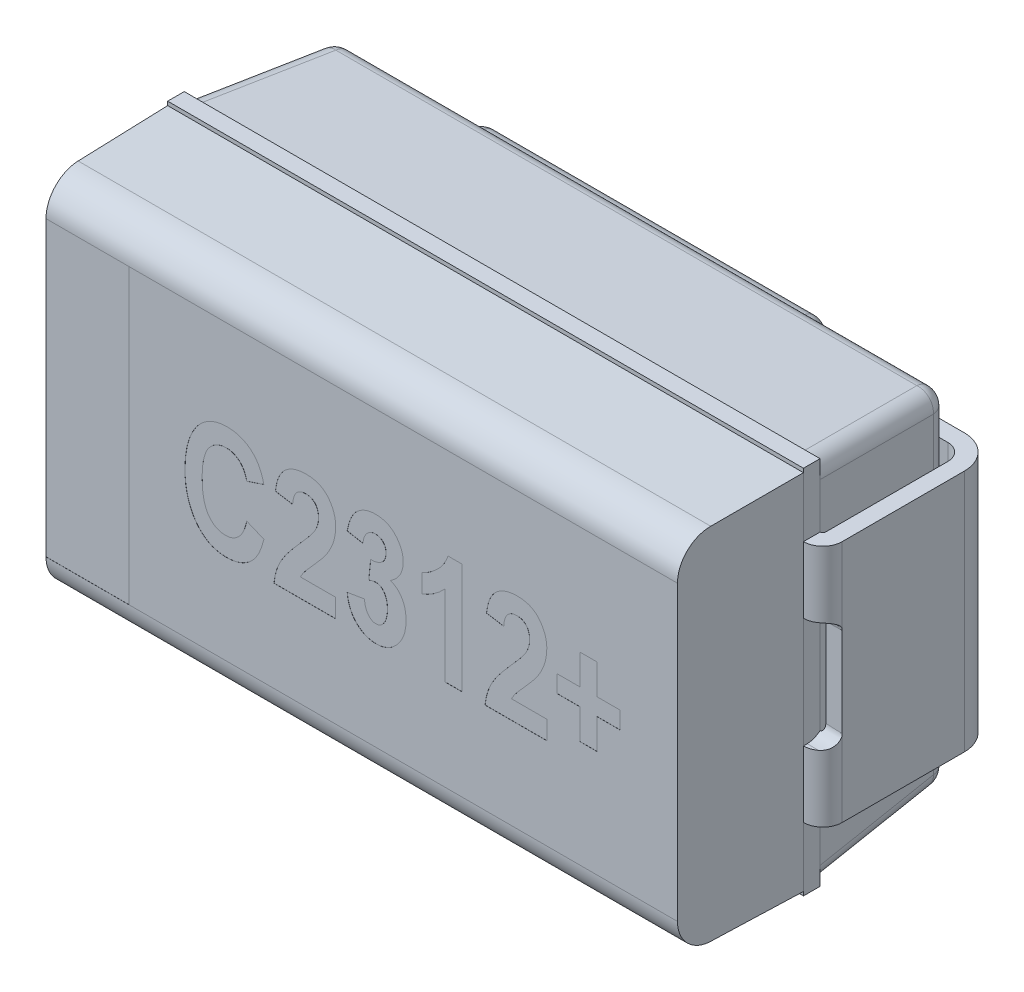
SolidWorks part; units mm, degrees
ref_plane "Front Plane" through (0, 0, 0) normal (0, 0, 1) x (1, 0, 0)
ref_plane "Top Plane" through (0, 0, 0) normal (0, 1, 0) x (1, 0, 0)
ref_plane "Right Plane" through (0, 0, 0) normal (1, 0, 0) x (0, 0, -1)
sketch "Sketch1" plane through (0, 0, 0) normal (0, 0, 1) x (1, 0, 0)
  line L1 (-2.875, 1.66) -> (2.875, 1.66)
  line L2 (-2.875, 1.66) -> (-2.875, -1.66)
  line L3 (-2.875, -1.66) -> (2.875, -1.66)
  line L4 (2.875, 1.66) -> (2.875, -1.66)
  line L5 (-2.875, 1.66) -> (2.875, -1.66) construction
  line L6 (-2.875, -1.66) -> (2.875, 1.66) construction
  point P0 (0, 0)
  dimension "D1" = 3.32
  dimension "D2" = 5.75
extrude "Boss-Extrude1" add sketch "Sketch1" against normal blind 1.26 draft 5 from offset 1.43 contours L2 L3 L4 L1
fillet "Fillet2" radius 0.15 8 edges at (-2.7648, 0, 0.17) (0, -1.5498, 0.17) (2.7648, 0, 0.17) (0, 1.5498, 0.17) (2.8199, 1.6049, 0.8) (-2.8199, 1.6049, 0.8) (2.8199, -1.6049, 0.8) (-2.8199, -1.6049, 0.8)
sketch "Sketch3" plane through (0, 0, 1.43) normal (0, 0, 1) x (1, 0, 0)
  line L0 (2.875, 1.5106) -> (2.875, -1.5106) construction
  line L1 (-2.875, 1.675) -> (2.875, 1.675)
  line L2 (-2.875, 1.675) -> (-2.875, -1.675)
  line L3 (-2.875, -1.675) -> (2.875, -1.675)
  line L4 (2.875, 1.675) -> (2.875, -1.675)
  line L5 (-2.875, 1.675) -> (2.875, -1.675) construction
  line L6 (-2.875, -1.675) -> (2.875, 1.675) construction
  point P0 (0, 0)
  dimension "D1" = 3.35
extrude "Boss-Extrude2" add sketch "Sketch3" along normal blind 0.15
sketch "Sketch4" plane through (0, 0, 1.58) normal (0, 0, 1) x (1, 0, 0)
  line L0 (2.875, -1.675) -> (2.875, 1.675) construction
  line L1 (-2.875, 1.64) -> (2.875, 1.64)
  line L2 (-2.875, 1.64) -> (-2.875, -1.64)
  line L3 (-2.875, -1.64) -> (2.875, -1.64)
  line L4 (2.875, 1.64) -> (2.875, -1.64)
  line L5 (-2.875, 1.64) -> (2.875, -1.64) construction
  line L6 (-2.875, -1.64) -> (2.875, 1.64) construction
  point P0 (0, 0)
  dimension "D1" = 3.28
extrude "Boss-Extrude4" add sketch "Sketch4" along normal blind 1.12 draft 1
fillet "Fillet4" radius 0.3012 2 edges at (0, -1.6205, 2.7) (0, 1.6205, 2.7)
sketch "Sketch5" plane through (0, 0, 0.17) normal (0, 0, -1) x (-1, 0, 0)
  line L1 (-1.6, 1.45) -> (1.6, 1.45)
  line L2 (-1.6, 1.45) -> (-1.6, -1.45)
  line L3 (-1.6, -1.45) -> (1.6, -1.45)
  line L4 (1.6, 1.45) -> (1.6, -1.45)
  line L5 (-1.6, 1.45) -> (1.6, -1.45) construction
  line L6 (-1.6, -1.45) -> (1.6, 1.45) construction
  point P0 (0, 0)
  dimension "D1" = 3.2
  dimension "D2" = 2.9
extrude "Boss-Extrude5" add sketch "Sketch5" along normal blind 0.16 from offset 0.01 offset against normal yes
fillet "Fillet5" radius 0.15 8 edges at (0, -1.45, 0.02) (1.6, 0, 0.02) (0, 1.45, 0.02) (-1.6, 0, 0.02) (-1.6, 1.45, 0.0974) (-1.6, -1.45, 0.0974) (1.6, 1.45, 0.0974) (1.6, -1.45, 0.0974)
sketch "Sketch7" plane through (0, 0, 0) normal (0, 1, 0) x (1, 0, 0)
  line L0 (2.875, -1.58) -> (2.875, -1.43)
  line L1 (2.9, -1.405) -> (2.9, -0.3)
  line L2 (2.75, -0.15) -> (1.779, -0.15)
  line L3 (1.779, -0.15) -> (1.779, 0)
  line L4 (1.779, 0) -> (2.75, 0)
  line L5 (3.05, -0.3) -> (3.05, -1.405)
  line L7 (2.6273, -0.17) -> (1.5494, -0.17) construction
  line L8 (0, 0) -> (0, -2.7) construction
  line L9 (-2.8555, -2.7) -> (2.8555, -2.7) construction
  line L10 (-3.05, -0.3) -> (-3.05, -1.405)
  line L11 (-1.779, 0) -> (-2.75, 0)
  line L12 (-1.779, -0.15) -> (-1.779, 0)
  line L13 (-2.75, -0.15) -> (-1.779, -0.15)
  line L14 (-2.9, -1.405) -> (-2.9, -0.3)
  line L15 (-2.875, -1.58) -> (-2.875, -1.43)
  arc A0 (2.875, -1.43) -> (2.9, -1.405) centre (2.875, -1.405) ccw
  arc A1 (2.9, -0.3) -> (2.75, -0.15) centre (2.75, -0.3) ccw
  arc A2 (2.75, 0) -> (3.05, -0.3) centre (2.75, -0.3) cw
  arc A3 (3.05, -1.405) -> (2.875, -1.58) centre (2.875, -1.405) cw
  arc A4 (-3.05, -1.405) -> (-2.875, -1.58) centre (-2.875, -1.405) ccw
  arc A5 (-2.75, 0) -> (-3.05, -0.3) centre (-2.75, -0.3) ccw
  arc A6 (-2.9, -0.3) -> (-2.75, -0.15) centre (-2.75, -0.3) cw
  arc A7 (-2.875, -1.43) -> (-2.9, -1.405) centre (-2.875, -1.405) cw
  dimension "D5" = 0.3
  dimension "D1" = 0.02
  dimension "D2" = 0.15
  dimension "D3" = 1.271
  dimension "D4" = 3.05
extrude "Boss-Extrude6" add sketch "Sketch7" along normal mid plane 2.2
sketch "Sketch9" plane through (-2.875, 0, 0) normal (-1, 0, 0) x (0, 0, 1)
  line L0 (1.58, 0.6867) -> (1.58, -0.6867)
  line L3 (0, 0) -> (2.7, 0) construction
  line L4 (2.7, 1.3245) -> (2.7, -1.3245) construction
  line L8 (0.7238, 0.4) -> (0.7238, -0.4)
  line L9 (0.8446, -0.5471) -> (1.3816, -0.6535)
  line L10 (1.3816, 0.6535) -> (0.8446, 0.5471)
  arc A2 (0.7238, -0.4) -> (0.8446, -0.5471) centre (0.8738, -0.4) ccw
  arc A3 (0.8446, 0.5471) -> (0.7238, 0.4) centre (0.8738, 0.4) ccw
  spline S2 degree 3 poles (1.58, -0.6867) (1.574, -0.6811) (1.55, -0.6756) (1.4777, -0.6645) (1.4298, -0.659) (1.3816, -0.6535) knots 0 0 0 0 0.5 0.5 1 1 1 1
  spline S3 degree 3 poles (1.58, 0.6867) (1.5792, 0.6859) (1.5767, 0.6843) (1.5707, 0.6818) (1.5621, 0.6792) (1.5513, 0.6767) (1.5383, 0.6741) (1.5233, 0.6715) (1.5065, 0.6689) (1.4882, 0.6664) (1.4685, 0.6638) (1.4478, 0.6612) (1.4262, 0.6586) (1.404, 0.656) (1.389, 0.6543) (1.3816, 0.6535) knots 0.004713 0.004713 0.004713 0.004713 0.008438 0.012657 0.016876 0.021095 0.025314 0.029533 0.033751 0.03797 0.042189 0.046408 0.050627 0.054846 0.059065 0.059065 0.059065 0.059065
extrude "Cut-Extrude2" cut sketch "Sketch9" along normal blind 2.4
sketch "Sketch10" plane through (0, 0, 2.7) normal (0, 0, 1) x (1, 0, 0)
  line L0 (-2.8555, -1.3245) -> (2.8555, -1.3245) construction
  line L1 (-2.8555, 1.3245) -> (-2.1055, 1.3245)
  line L2 (-2.8555, 1.3245) -> (-2.8555, -1.3245)
  line L3 (-2.8555, -1.3245) -> (-2.1055, -1.3245)
  line L4 (-2.1055, 1.3245) -> (-2.1055, -1.3245)
  line L5 (-2.1055, -0.5) -> (2.8555, -0.5) construction
  line L6 (2.8555, -1.3245) -> (2.8555, 1.3245) construction
  line L8 (1.485, 0) -> (-1.485, 0) construction
  text T0 "<b>C2312+</b>" font "Arial Narrow" height 1
  dimension "D1" = 0.75
  dimension "D2" = 0.5
extrude "Cut-Extrude3" cut sketch "Sketch10" against normal blind 0.001
sketch "Sketch12" plane through (2.875, 0, 0) normal (1, 0, 0) x (0, 0, -1)
  line L0 (-1.58, 0.5) -> (-1.58, -0.5)
  line L1 (0, 0) -> (-2.7, 0) construction
  line L2 (-2.7, -1.3245) -> (-2.7, 1.3245) construction
  line L3 (-1.5462, -0.5) -> (-1.58, -0.5)
  line L4 (-1.4026, 0.4) -> (-1.4026, -0.4)
  line L5 (-1.58, 0.5) -> (-1.5462, 0.5)
  spline S2 degree 3 poles (-1.4026, -0.4) (-1.4033, -0.4073) (-1.4048, -0.4222) (-1.4169, -0.4428) (-1.4354, -0.4607) (-1.4656, -0.48) (-1.5077, -0.4969) (-1.533, -0.4989) (-1.5462, -0.5) knots 0 0 0 0 0.100894 0.204467 0.32118 0.458503 0.717255 1 1 1 1
  spline S3 degree 3 poles (-1.5462, 0.5) (-1.5375, 0.4995) (-1.5206, 0.4985) (-1.489, 0.4897) (-1.4571, 0.4751) (-1.4284, 0.4557) (-1.4066, 0.4298) (-1.4039, 0.4097) (-1.4026, 0.4) knots 0 0 0 0 0.195151 0.376782 0.549697 0.724506 0.867709 1 1 1 1
extrude "Cut-Extrude4" cut sketch "Sketch12" along normal up to next
